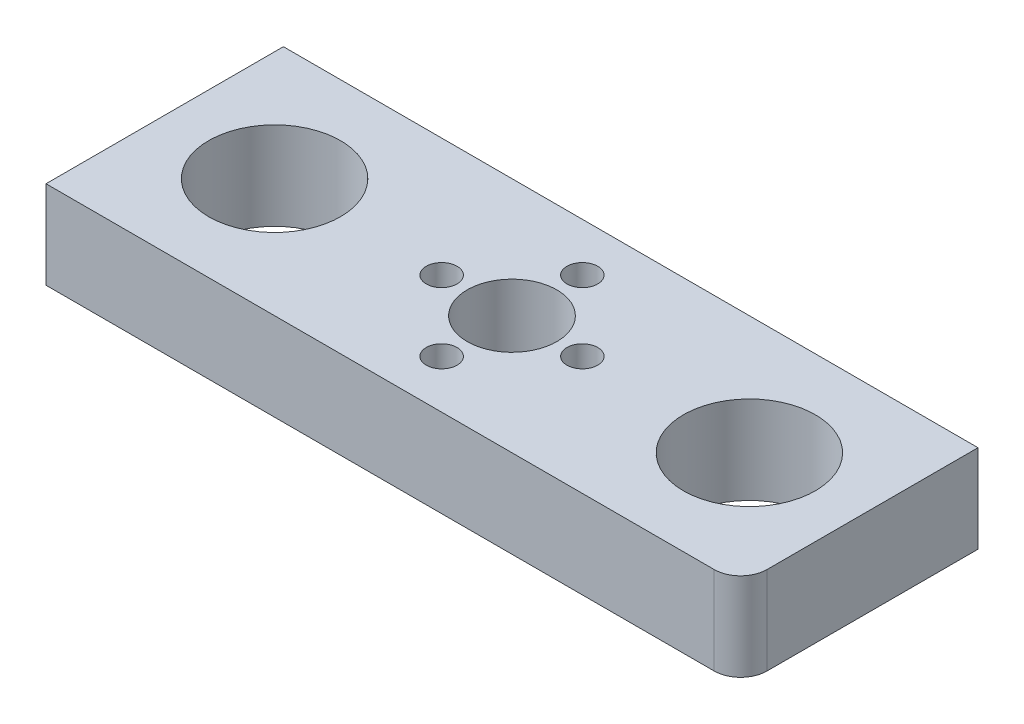
SolidWorks part; units mm, degrees
ref_plane "前视基准面" through (0, 0, 0) normal (0, 0, 1) x (1, 0, 0)
ref_plane "上视基准面" through (0, 0, 0) normal (0, 1, 0) x (1, 0, 0)
ref_plane "右视基准面" through (0, 0, 0) normal (1, 0, 0) x (0, 0, -1)
sketch "草图1" plane through (0, 0, 0) normal (0, 1, 0) x (1, 0, 0)
  line L1 (-39.5, 13.5) -> (39.5, 13.5)
  line L2 (-39.5, 13.5) -> (-39.5, -13.5)
  line L3 (-39.5, -13.5) -> (39.5, -13.5)
  line L4 (39.5, 13.5) -> (39.5, -13.5)
  line L5 (-39.5, 13.5) -> (39.5, -13.5) construction
  line L6 (-39.5, -13.5) -> (39.5, 13.5) construction
  point P0 (0, 0)
  dimension "D1" = 79
  dimension "D2" = 27
extrude "凸台-拉伸1" add sketch "草图1" along normal blind 10
sketch "草图2" plane through (0, 0, 0) normal (0, -1, 0) x (1, 0, 0)
  line L0 (-39.5, 0) -> (39.5, 0) construction
  line L1 (-39.5, -13.5) -> (-39.5, 13.5) construction
  line L2 (39.5, 13.5) -> (39.5, -13.5) construction
ref_plane "基准面1" through (0, 0, 0) normal (0, 0, 1) x (1, 0, 0)
sketch "草图3" plane through (0, 10, 0) normal (0, 1, 0) x (1, 0, 0)
  line L0 (-14.85, 0) -> (14.85, 0) construction
  line L1 (0, 13.5) -> (0, -13.5) construction
  line L2 (39.5, 13.5) -> (-39.5, 13.5) construction
  line L3 (-39.5, -13.5) -> (39.5, -13.5) construction
  circle A0 centre (-27, 0) radius 7.5
  circle A1 centre (27, 0) radius 7.5
  dimension "D1" = 15
  dimension "D2" = 54
extrude "切除-拉伸1" cut sketch "草图3" against normal through all contours A1 | A0
fillet "圆角1" radius 3 1 edges at (39.5, 5, 13.5)
sketch "草图4" plane through (0, 10, 0) normal (0, 1, 0) x (1, 0, 0)
  circle A0 centre (0, 0) radius 5.1
  dimension "D1" = 10.2
extrude "切除-拉伸2" cut sketch "草图4" against normal through all
sketch "草图5" plane through (0, 10, 0) normal (0, 1, 0) x (1, 0, 0)
  circle A0 centre (8, 0) radius 1.75
  circle A1 centre (0, -8) radius 1.75
  circle A2 centre (-8, 0) radius 1.75
  circle A3 centre (0, 8) radius 1.75
  dimension "D1" = 3.5
extrude "切除-拉伸3" cut sketch "草图5" against normal through all
